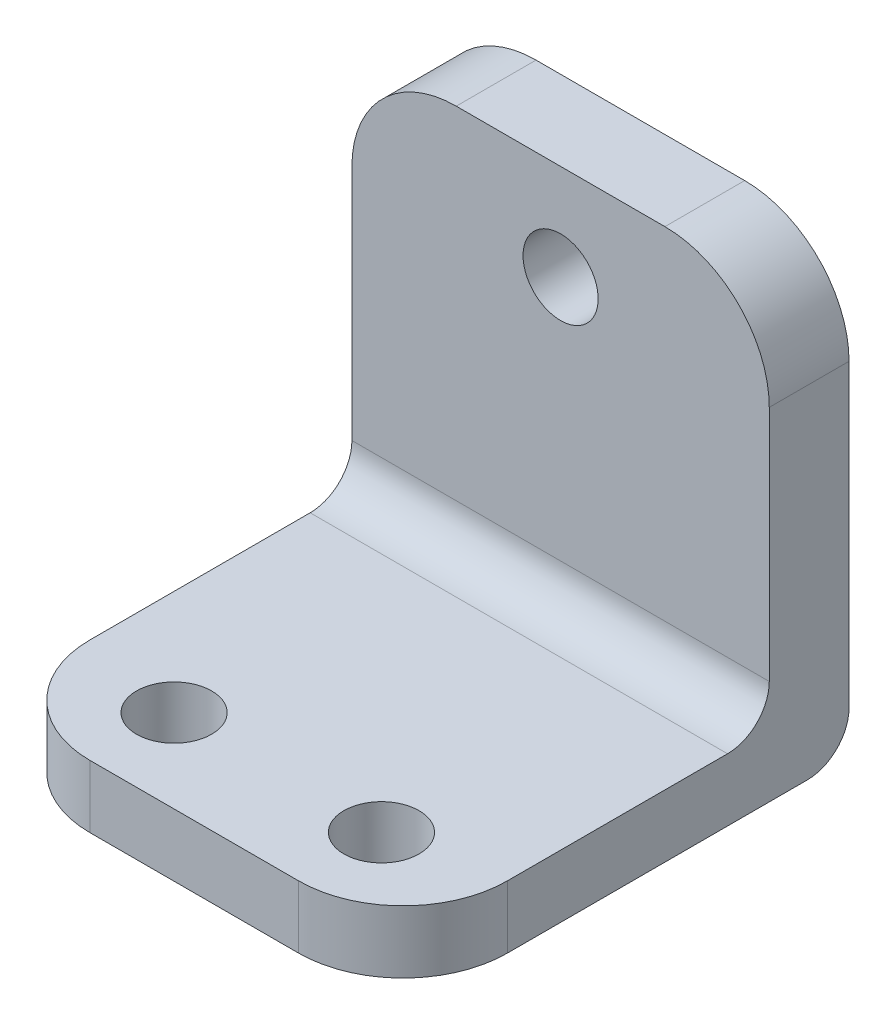
SolidWorks part; units mm, degrees
ref_plane "Alzado" through (0, 0, 0) normal (0, 0, 1) x (1, 0, 0)
ref_plane "Planta" through (0, 0, 0) normal (0, 1, 0) x (1, 0, 0)
ref_plane "Vista lateral" through (0, 0, 0) normal (1, 0, 0) x (0, 0, -1)
sketch "Croquis1" plane through (0, 0, 0) normal (0, 1, 0) x (1, 0, 0)
  line L1 (-10, 10.6875) -> (10, 10.6875)
  line L2 (-10, 10.6875) -> (-10, -10.6875)
  line L3 (-10, -10.6875) -> (10, -10.6875)
  line L4 (10, 10.6875) -> (10, -10.6875)
  line L5 (-10, 10.6875) -> (10, -10.6875) construction
  line L6 (-10, -10.6875) -> (10, 10.6875) construction
  point P0 (0, 0)
  dimension "D1" = 20
  dimension "D2" = 21.375
extrude "Saliente-Extruir1" add sketch "Croquis1" along normal blind 3
sketch "Croquis2" plane through (0, 3, 0) normal (0, 1, 0) x (1, 0, 0)
  line L0 (-10, 10.6875) -> (-10, -10.6875) construction
  line L1 (10, 10.6875) -> (-10, 10.6875)
  line L2 (10, 10.6875) -> (10, 6.8643)
  line L3 (10, 6.8643) -> (-10, 6.8643)
  line L4 (-10, 10.6875) -> (-10, 6.8643)
extrude "Saliente-Extruir2" add sketch "Croquis2" along normal blind 18.375
sketch "Croquis3" plane through (0, 0, 0) normal (0, -1, 0) x (1, 0, 0)
  line L0 (10, 6.6875) -> (-10, 6.6875) construction
  line L1 (10, 10.6875) -> (10, -10.6875) construction
  line L2 (-10, -10.6875) -> (-10, 10.6875) construction
  line L3 (0, 10.6875) -> (0, -10.6875) construction
  line L4 (-10, 10.6875) -> (10, 10.6875) construction
  line L5 (10, -10.6875) -> (-10, -10.6875) construction
  line L6 (-10, 10.6875) -> (10, 10.6875) construction
  circle A0 centre (4.9689, 6.6875) radius 1.8
  circle A1 centre (-4.9689, 6.6875) radius 1.8
  dimension "D1" = 3.6
  dimension "D2" = 4
extrude "Cortar-Extruir1" cut sketch "Croquis3" against normal blind 20
sketch "Croquis4" plane through (0, 0, -10.6875) normal (0, 0, -1) x (-1, 0, 0)
  circle A0 centre (0, 16.7773) radius 1.8
  dimension "D1" = 3.6
extrude "Cortar-Extruir2" cut sketch "Croquis4" against normal blind 20
fillet "Redondeo1" radius 5 4 edges at (-10, 21.375, -8.7759) (10, 1.5, 10.6875) (-10, 1.5, 10.6875) (10, 21.375, -8.7759)
fillet "Redondeo2" radius 2 2 edges at (0, 0, -10.6875)
